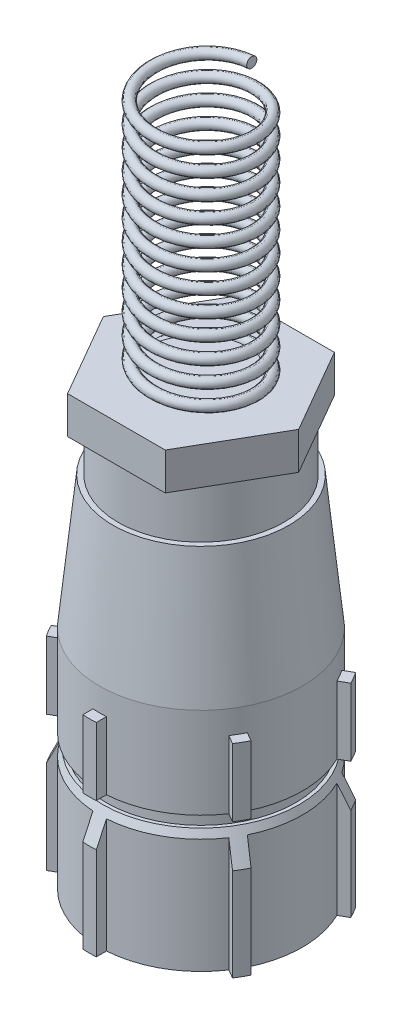
SolidWorks part; units mm, degrees
ref_plane "Спереди" through (0, 0, 0) normal (0, 0, 1) x (1, 0, 0)
ref_plane "Сверху" through (0, 0, 0) normal (0, 1, 0) x (1, 0, 0)
ref_plane "Справа" through (0, 0, 0) normal (1, 0, 0) x (0, 0, -1)
sketch "Эскиз1" plane through (0, 0, 0) normal (0, 1, 0) x (1, 0, 0)
  circle A0 centre (0, 0) radius 15
  dimension "D1" = 30
extrude "Бобышка-Вытянуть1" add sketch "Эскиз1" along normal blind 33
sketch "Эскиз2" plane through (0, 0, 0) normal (0, -1, 0) x (1, 0, 0)
  line L0 (0, 16.5) -> (0, -16.5) construction
  line L1 (-1, 16.4697) -> (-1, 14.9666)
  line L2 (1, 16.4697) -> (1, 14.9666)
  line L3 (13.7632, 9.1009) -> (12.4615, 8.3493)
  line L4 (14.7632, 7.3688) -> (13.4615, 6.6173)
  line L5 (14.7632, -7.3688) -> (13.4615, -6.6173)
  line L6 (13.7632, -9.1009) -> (12.4615, -8.3493)
  line L7 (1, -16.4697) -> (1, -14.9666)
  line L8 (-1, -16.4697) -> (-1, -14.9666)
  line L9 (-13.7632, -9.1009) -> (-12.4615, -8.3493)
  line L10 (-14.7632, -7.3688) -> (-13.4615, -6.6173)
  line L11 (-14.7632, 7.3688) -> (-13.4615, 6.6173)
  line L12 (-13.7632, 9.1009) -> (-12.4615, 8.3493)
  arc A0 (-13.7632, 9.1009) -> (-14.7632, 7.3688) centre (0, 0) ccw
  circle A1 centre (0, 0) radius 15 construction
  circle A2 centre (0, 0) radius 15
  arc A3 (1, 16.4697) -> (-1, 16.4697) centre (0, 0) ccw
  arc A4 (14.7632, 7.3688) -> (13.7632, 9.1009) centre (0, 0) ccw
  arc A5 (13.7632, -9.1009) -> (14.7632, -7.3688) centre (0, 0) ccw
  arc A6 (-1, -16.4697) -> (1, -16.4697) centre (0, 0) ccw
  arc A7 (-14.7632, -7.3688) -> (-13.7632, -9.1009) centre (0, 0) ccw
  point P34 (0, 0)
  circle M13 centre (0, 0) radius 15
  dimension "D1" = 33
  dimension "D2" = 2
  dimension "D3" = 6
extrude "Бобышка-Вытянуть2" add sketch "Эскиз2" against normal blind 10 contours A3 L0 L2 M13 | L0 A3 L1 A2 | L12 A0 L11 M13 | L4 A4 L3 M13 | L6 A5 L5 M13 | L0 L8 A6 M13 | A2 L0 A6 L7 | L10 A7 L9 M13
sketch "Эскиз3" plane through (0, 33, 0) normal (0, 1, 0) x (1, 0, 0)
  circle A3 centre (0, 0) radius 12.25
  dimension "D2" = 24.5
extrude "Бобышка-Вытянуть3" add sketch "Эскиз3" along normal blind 13 separate body
sketch "Эскиз5" plane through (0, 0, 0) normal (0, -1, 0) x (1, 0, 0)
  circle A0 centre (0, 0) radius 14
  dimension "D1" = 28
extrude "Бобышка-Вытянуть4" add sketch "Эскиз5" along normal blind 2
sketch "Эскиз6" plane through (0, -2, 0) normal (0, -1, 0) x (1, 0, 0)
  circle A0 centre (0, 0) radius 16.5
  dimension "D1" = 33
extrude "Бобышка-Вытянуть5" add sketch "Эскиз6" along normal blind 19
sketch "Эскиз7" plane through (0, -21, 0) normal (0, -1, 0) x (1, 0, 0)
  circle A0 centre (0, 0) radius 11
  circle A1 centre (0, 0) radius 13.5
  dimension "D1" = 22
  dimension "D2" = 27
extrude "Вырез-Вытянуть2" cut sketch "Эскиз7" against normal blind 9
sketch "Эскиз8" plane through (0, -21, 0) normal (0, -1, 0) x (1, 0, 0)
  circle A0 centre (0, 0) radius 13.5 construction
  circle A1 centre (0, 0) radius 16.5
  circle A2 centre (0, 0) radius 16.5
  circle A3 centre (0, 0) radius 13.5
  dimension "D1" = 0
extrude "Вырез-Вытянуть3" cut sketch "Эскиз8" against normal blind 1
sketch "Эскиз9" plane through (0, -21, 0) normal (0, -1, 0) x (1, 0, 0)
  circle A0 centre (0, 0) radius 0.75
  circle A1 centre (3, 0) radius 0.75
  circle A2 centre (6, 0) radius 0.75
  circle A3 centre (9, 0) radius 0.75
  circle A4 centre (4.5, -7.7942) radius 0.75
  circle A5 centre (3, -5.1962) radius 0.75
  circle A6 centre (1.5, -2.5981) radius 0.75
  circle A7 centre (0, 0) radius 0.75
  circle A8 centre (-4.5, -7.7942) radius 0.75
  circle A9 centre (-3, -5.1962) radius 0.75
  circle A10 centre (-1.5, -2.5981) radius 0.75
  circle A11 centre (0, 0) radius 0.75
  circle A12 centre (-9, 0) radius 0.75
  circle A13 centre (-6, 0) radius 0.75
  circle A14 centre (-3, 0) radius 0.75
  circle A15 centre (0, 0) radius 0.75
  circle A16 centre (-4.5, 7.7942) radius 0.75
  circle A17 centre (-3, 5.1962) radius 0.75
  circle A18 centre (-1.5, 2.5981) radius 0.75
  circle A19 centre (0, 0) radius 0.75
  circle A20 centre (4.5, 7.7942) radius 0.75
  circle A21 centre (3, 5.1962) radius 0.75
  circle A22 centre (1.5, 2.5981) radius 0.75
  circle A23 centre (0, 0) radius 0.75
  point P47 (0, 0)
  dimension "D1" = 1.5
  dimension "D2" = 3
  dimension "D3" = 3
  dimension "D4" = 3
  dimension "D5" = 6
extrude "Вырез-Вытянуть4" cut sketch "Эскиз9" against normal blind 4 contours A10 | A14 | A0 | A6 | A1 | A5 | A2 | A9 | A8 | A4 | A3 | A13 | A12 | A18 | A22 | A21 | A20 | A17 | A16
chamfer "Фаска1" distance 2 angle 65 1 edges at (0, -2, -16.5)
sketch "Эскиз10" plane through (0, -20, 0) normal (0, -1, 0) x (1, 0, 0)
  line L12 (1, 14.9666) -> (1, 16.4697)
  line L13 (-1, 16.4697) -> (-1, 14.9666)
  line L14 (-12.4615, 8.3493) -> (-13.7632, 9.1009)
  line L15 (-14.7632, 7.3688) -> (-13.4615, 6.6173)
  line L16 (-13.4615, -6.6173) -> (-14.7632, -7.3688)
  line L17 (-13.7632, -9.1009) -> (-12.4615, -8.3493)
  line L18 (-1, -14.9666) -> (-1, -16.4697)
  line L19 (1, -16.4697) -> (1, -14.9666)
  line L20 (12.4615, -8.3493) -> (13.7632, -9.1009)
  line L21 (14.7632, -7.3688) -> (13.4615, -6.6173)
  line L22 (13.4615, 6.6173) -> (14.7632, 7.3688)
  line L23 (13.7632, 9.1009) -> (12.4615, 8.3493)
  line L24 (1, 14.9666) -> (1, 16.4697)
  line L25 (-1, 16.4697) -> (-1, 14.9666)
  line L26 (-12.4615, 8.3493) -> (-13.7632, 9.1009)
  line L27 (-14.7632, 7.3688) -> (-13.4615, 6.6173)
  line L28 (-13.4615, -6.6173) -> (-14.7632, -7.3688)
  line L29 (-13.7632, -9.1009) -> (-12.4615, -8.3493)
  line L30 (-1, -14.9666) -> (-1, -16.4697)
  line L31 (1, -16.4697) -> (1, -14.9666)
  line L32 (12.4615, -8.3493) -> (13.7632, -9.1009)
  line L33 (14.7632, -7.3688) -> (13.4615, -6.6173)
  line L34 (13.4615, 6.6173) -> (14.7632, 7.3688)
  line L35 (13.7632, 9.1009) -> (12.4615, 8.3493)
  circle A0 centre (0, 0) radius 16.5 construction
  arc A1 (-1, 16.4697) -> (-13.7632, 9.1009) centre (0, 0) ccw
  arc A2 (-14.7632, 7.3688) -> (-14.7632, -7.3688) centre (0, 0) ccw
  arc A3 (13.7632, 9.1009) -> (1, 16.4697) centre (0, 0) ccw
  arc A4 (14.7632, -7.3688) -> (14.7632, 7.3688) centre (0, 0) ccw
  arc A5 (1, -16.4697) -> (13.7632, -9.1009) centre (0, 0) ccw
  arc A6 (-13.7632, -9.1009) -> (-1, -16.4697) centre (0, 0) ccw
  arc A12 (12.4615, 8.3493) -> (1, 14.9666) centre (0, 0) ccw
  arc A13 (1, 16.4697) -> (-1, 16.4697) centre (0, 0) ccw
  arc A14 (-1, 14.9666) -> (-12.4615, 8.3493) centre (0, 0) ccw
  arc A15 (-13.7632, 9.1009) -> (-14.7632, 7.3688) centre (0, 0) ccw
  arc A16 (-13.4615, 6.6173) -> (-13.4615, -6.6173) centre (0, 0) ccw
  arc A17 (-14.7632, -7.3688) -> (-13.7632, -9.1009) centre (0, 0) ccw
  arc A18 (-12.4615, -8.3493) -> (-1, -14.9666) centre (0, 0) ccw
  arc A19 (-1, -16.4697) -> (1, -16.4697) centre (0, 0) ccw
  arc A20 (1, -14.9666) -> (12.4615, -8.3493) centre (0, 0) ccw
  arc A21 (13.7632, -9.1009) -> (14.7632, -7.3688) centre (0, 0) ccw
  arc A22 (13.4615, -6.6173) -> (13.4615, 6.6173) centre (0, 0) ccw
  arc A23 (14.7632, 7.3688) -> (13.7632, 9.1009) centre (0, 0) ccw
  arc A24 (12.4615, 8.3493) -> (1, 14.9666) centre (0, 0) ccw
  arc A26 (-1, 14.9666) -> (-12.4615, 8.3493) centre (0, 0) ccw
  arc A28 (-13.4615, 6.6173) -> (-13.4615, -6.6173) centre (0, 0) ccw
  arc A30 (-12.4615, -8.3493) -> (-1, -14.9666) centre (0, 0) ccw
  arc A32 (1, -14.9666) -> (12.4615, -8.3493) centre (0, 0) ccw
  arc A34 (13.4615, -6.6173) -> (13.4615, 6.6173) centre (0, 0) ccw
  dimension "D1" = 0
extrude "Вырез-Вытянуть5" cut sketch "Эскиз10" against normal blind 18
sketch "Эскиз11" plane through (0, 33, 0) normal (0, 1, 0) x (1, 0, 0)
  circle A0 centre (0, 0) radius 7.5
  dimension "D1" = 15
extrude "Бобышка-Вытянуть6" add sketch "Эскиз11" along normal blind 1
sketch "Эскиз14" plane through (0, 34, 0) normal (0, 1, 0) x (1, 0, 0)
  circle A1 centre (0, 0) radius 7.5
  dimension "D1" = 15
curve "Спираль1" pitch 3 height 48 turns 16
sketch "Эскиз15" plane through (0, 0, 0) normal (1, 0, 0) x (0, 0, -1)
  circle A0 centre (7.5, 34) radius 0.75
  point P7 (0, 0)
  dimension "D1" = 1.5
sweep "По траектории1" add profiles "Эскиз15" path "Спираль1"
sketch "Эскиз18" plane through (0, 46, 0) normal (0, 1, 0) x (1, 0, 0)
  line L1 (14.4338, 0) -> (7.2169, 12.5)
  line L2 (7.2169, 12.5) -> (-7.2169, 12.5)
  line L3 (-7.2169, 12.5) -> (-14.4338, 0)
  line L4 (-14.4338, 0) -> (-7.2169, -12.5)
  line L5 (-7.2169, -12.5) -> (7.2169, -12.5)
  line L6 (7.2169, -12.5) -> (14.4338, 0)
  circle A0 centre (0, 0) radius 12.5 construction
  dimension "D1" = 25
extrude "Бобышка-Вытянуть8" add sketch "Эскиз18" against normal blind 5.5
sketch "Эскиз19" plane through (0, 0, 0) normal (0, 0, 1) x (1, 0, 0)
  line L0 (-15, 33) -> (-15, 13.4256)
  line L1 (-15, 33) -> (-15, 0) construction
  line L2 (-15, 13.4256) -> (-13, 33)
  line L3 (15, 33) -> (-15, 33) construction
  line L4 (-13, 33) -> (-15, 33)
  line L5 (0, -21) -> (0, 86.4242) construction
  line L6 (-11, -21) -> (11, -21) construction
  dimension "D1" = 2
revolve "Вырез-Повернуть1" cut sketch "Эскиз19" angle 360 about L5
